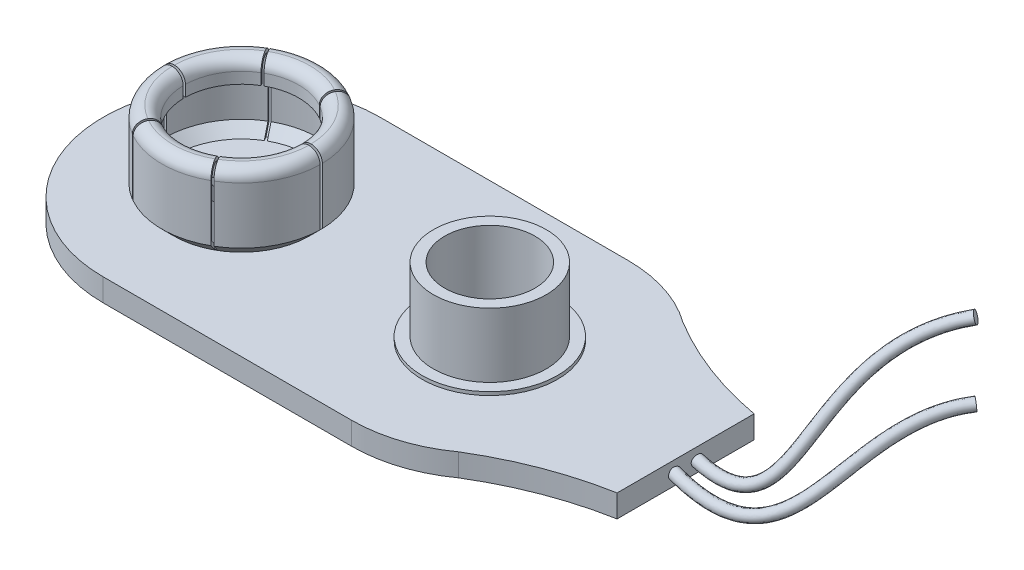
SolidWorks part; units mm, degrees
ref_plane "Front Plane" through (0, 0, 0) normal (0, 0, 1) x (1, 0, 0)
ref_plane "Top Plane" through (0, 0, 0) normal (0, 1, 0) x (1, 0, 0)
ref_plane "Right Plane" through (0, 0, 0) normal (1, 0, 0) x (0, 0, -1)
sketch "Sketch2" plane through (0, 0, 0) normal (0, 1, 0) x (1, 0, 0)
  line L1 (-12.5, -8) -> (12.5, -8)
  line L2 (-12.5, -8) -> (-12.5, 8)
  line L3 (-12.5, 8) -> (12.5, 8)
  line L4 (12.5, -8) -> (12.5, 8)
  line L5 (-12.5, -8) -> (12.5, 8) construction
  line L6 (-12.5, 8) -> (12.5, -8) construction
  point P0 (0, 0)
  dimension "D1" = 25
  dimension "D2" = 16
extrude "Boss-Extrude1" add sketch "Sketch2" along normal blind 46
fillet "Fillet1" radius 4 4 edges at (-12.5, 23, -8) (-12.5, 23, 8) (12.5, 23, -8) (12.5, 23, 8)
fillet "Fillet2" radius 1 16 edges at (-11.3284, 0, 6.8284) (0, 0, 8) (11.3284, 0, 6.8284) (12.5, 0, 0) (11.3284, 0, -6.8284) (0, 0, -8) (-11.3284, 0, -6.8284) (-12.5, 0, 0) (11.3284, 46, -6.8284) (12.5, 46, 0) (11.3284, 46, 6.8284) (0, 46, 8) (-11.3284, 46, 6.8284) (-12.5, 46, 0) (-11.3284, 46, -6.8284) (0, 46, -8)
sketch "Sketch3" plane through (0, 46, 0) normal (0, 1, 0) x (1, 0, 0)
  circle A0 centre (5.5, 0) radius 2.5
  dimension "D1" = 5
  dimension "D2" = 5.5
sketch "Sketch6" plane through (0, 46, 0) normal (0, 1, 0) x (1, 0, 0)
  circle A0 centre (-5.5, 0) radius 1
  circle A1 centre (5.5, 0) radius 1
  dimension "D1" = 2
  dimension "D2" = 2
  dimension "D3" = 11
  dimension "D4" = 5.5
extrude "Extrude-Thin1" add sketch "Sketch3" along normal blind 3 thin thin type one direction reverse wall 0.5
extrude "Boss-Extrude2" add sketch "Sketch6" along normal blind 0.75
ref_axis "Axis1" through (-5.5, 46.75, 0) along (0, -1, 0)
sketch "Sketch9" plane through (0, 0, 0) normal (0, 0, 1) x (1, 0, 0)
  line L0 (-4.5, 46) -> (-2.5, 46)
  line L2 (-2.5, 46) -> (-1.9697, 46.5303)
  line L3 (-1.9697, 46.5303) -> (-1.9697, 49.0303)
  line L5 (-2.9642, 49.0303) -> (-2.9642, 48.5352)
  arc A0 (-2.4691, 49.5255) -> (-2.9642, 49.0303) centre (-2.4691, 49.0303) ccw
  arc A1 (-1.9697, 49.0303) -> (-2.4691, 49.5255) centre (-2.4648, 49.0303) ccw
  dimension "D1" = 2
  dimension "D2" = 2.5
  dimension "D3" = 0.75
revolve "Revolve-Thin1" add sketch "Sketch9" angle 360 about axis through (-5.5, 46.75, 0) along (0, -1, 0) wall 0.15 other way angle 360
sketch "Sketch10" plane through (0, 46.15, 0) normal (0, 1, 0) x (1, 0, 0)
  line L1 (-3.2191, -0.05) -> (-1.7191, -0.05)
  line L2 (-3.2191, -0.05) -> (-3.2191, 0.05)
  line L3 (-3.2191, 0.05) -> (-1.7191, 0.05)
  line L4 (-1.7191, -0.05) -> (-1.7191, 0.05)
  line L5 (-3.2191, -0.05) -> (-1.7191, 0.05) construction
  line L6 (-3.2191, 0.05) -> (-1.7191, -0.05) construction
  circle A0 centre (-5.5, 0) radius 3.0309 construction
  point P0 (-2.4691, 0)
  dimension "D1" = 0.1
  dimension "D2" = 1.5
extrude "Cut-Extrude1" cut sketch "Sketch10" along normal through all
pattern_circular "CirPattern1" count 6 over 360 about axis through (-5.5, 46.75, 0) along (0, -1, 0) of "Cut-Extrude1"
sketch "Sketch11" plane through (0, 46, 0) normal (0, 1, 0) x (1, 0, 0)
  circle A0 centre (5.5, 0) radius 3
  dimension "D1" = 6
extrude "Boss-Extrude3" add sketch "Sketch11" along normal blind 0.15
sketch "Sketch12" plane through (0, 0, 0) normal (0, -1, 0) x (1, 0, 0)
  line L1 (-20.173, 15.0884) -> (20.173, 15.0884)
  line L2 (-20.173, 15.0884) -> (-20.173, -15.0884)
  line L3 (-20.173, -15.0884) -> (20.173, -15.0884)
  line L4 (20.173, 15.0884) -> (20.173, -15.0884)
  line L5 (-20.173, 15.0884) -> (20.173, -15.0884) construction
  line L6 (-20.173, -15.0884) -> (20.173, 15.0884) construction
  point P0 (0, 0)
extrude "Cut-Extrude2" cut sketch "Sketch12" against normal up to surface (46 mm away) up to face at (5.5, 46, -3)
sketch "Sketch13" plane through (0, 46, 0) normal (0, -1, 0) x (1, 0, 0)
  line L1 (-5.5, 6.129) -> (5.5, 6.129)
  line L3 (-5.5, -6.129) -> (5.5, -6.129)
  arc A1 (5.5, -6.129) -> (5.5, 6.129) centre (5.5, 0) ccw
  arc A2 (-5.5, 6.129) -> (-5.5, -6.129) centre (-5.5, 0) ccw
  point P0 (0, 0)
extrude "Boss-Extrude4" add sketch "Sketch13" along normal blind 0.5
sketch "Sketch14" plane through (0, 46, 0) normal (0, 1, 0) x (1, 0, 0)
  line L0 (14.1742, 0) -> (15.8816, 0)
  line L4 (14.1742, 3.0354) -> (14.1742, -3.0354)
  line L7 (9.0839, 4.972) -> (8.3473, 3.469)
  line L8 (8.3473, 3.469) -> (9.0839, -3.0354)
  line L9 (9.0839, -4.972) -> (9.0839, -3.0354)
  arc A0 (5.5, -6.129) -> (5.5, 6.129) centre (5.5, 0) ccw construction
  arc A1 (9.0839, 4.972) -> (14.1742, 3.0354) centre (16.8231, 17.6559) ccw
  arc A2 (9.0839, -4.972) -> (14.1742, -3.0354) centre (16.8231, -17.6559) cw
  point P0 (11.629, 0)
  arc M6 (5.5, -6.129) -> (5.5, 6.129) centre (5.5, 0) ccw
extrude "Boss-Extrude5" add sketch "Sketch14" against normal blind 0.5 contours A2 L4 A1 M6 region at (12.4971, 46, 0)
sketch "Sketch15" plane through (0, 45.5, 0) normal (0, -1, 0) x (1, 0, 0)
  line L3 (-5.5, -6.129) -> (5.5, -6.129)
  line L4 (14.1742, -3.0354) -> (14.1742, 3.0354)
  line L5 (5.5, 6.129) -> (-5.5, 6.129)
  line L6 (-5.5, -6.129) -> (5.5, -6.129)
  line L7 (14.1742, -3.0354) -> (14.1742, 3.0354)
  line L8 (5.5, 6.129) -> (-5.5, 6.129)
  arc A5 (-5.5, 6.129) -> (-5.5, -6.129) centre (-5.5, 0) ccw
  arc A6 (5.5, -6.129) -> (9.0839, -4.972) centre (5.5, 0) ccw
  arc A7 (14.1742, -3.0354) -> (9.0839, -4.972) centre (16.8231, -17.6559) ccw
  arc A8 (9.0839, 4.972) -> (14.1742, 3.0354) centre (16.8231, 17.6559) ccw
  arc A9 (9.0839, 4.972) -> (5.5, 6.129) centre (5.5, 0) ccw
  arc A10 (-5.5, 6.129) -> (-5.5, -6.129) centre (-5.5, 0) ccw
  arc A11 (5.5, -6.129) -> (9.0839, -4.972) centre (5.5, 0) ccw
  arc A12 (14.1742, -3.0354) -> (9.0839, -4.972) centre (16.8231, -17.6559) ccw
  arc A13 (9.0839, 4.972) -> (14.1742, 3.0354) centre (16.8231, 17.6559) ccw
  arc A14 (9.0839, 4.972) -> (5.5, 6.129) centre (5.5, 0) ccw
  dimension "D1" = 0
extrude "Boss-Extrude6" add sketch "Sketch15" along normal blind 0.5
sketch "Wires" plane through (14.1742, 0, 0) normal (1, 0, 0) x (0, 0, -1)
  line L0 (0.5, 45.5) -> (-0.5, 45.5) construction
  circle A0 centre (-0.5, 45.5) radius 0.3043
  circle A1 centre (0.5, 45.5) radius 0.3043
  point P3 (0, 45.5)
  dimension "D1" = 1
sketch3d "PostiveLead3DSketch"
  line L0 (20.4654, 52.2361, -6.5644) -> (20.4654, 49.9501, -6.5644) construction
  spline S0 degree 3 poles (20.4654, 51.0931, -6.5644) (16.1471, 49.5817, -3.1186) (19.1671, 44.474, -0.1811) (14.1742, 45.5, -0.5) knots 0 0 0 0 1 1 1 1
sweep "PositiveLead" add path "PostiveLead3DSketch" circular profile diameter 0.5 parameters "D3"=0.5
sketch3d "NegativeLead3DSketch"
  line L0 (20.4654, 48.9002, -6.5644) -> (20.4654, 46.6142, -6.5644) construction
  spline S0 degree 3 poles (20.4654, 47.7572, -6.5644) (17.7839, 47.4888, -3.1167) (20.9957, 44.9803, 1.9609) (14.1742, 45.5, 0.5) knots 0 0 0 0 1 1 1 1
sweep "NegativeLead" add path "NegativeLead3DSketch" circular profile diameter 0.5 parameters "D3"=0.5
